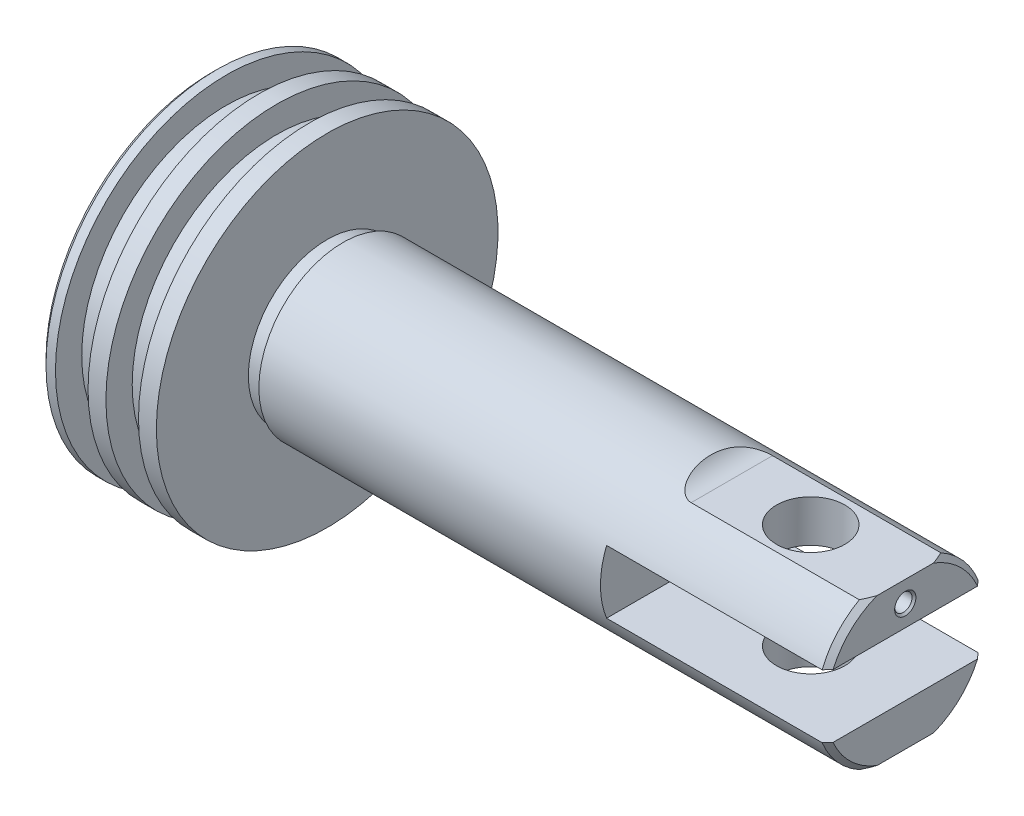
SolidWorks part; units mm, degrees
ref_plane "前视基准面" through (0, 0, 0) normal (0, 0, 1) x (1, 0, 0)
ref_plane "上视基准面" through (0, 0, 0) normal (0, 1, 0) x (1, 0, 0)
ref_plane "右视基准面" through (0, 0, 0) normal (1, 0, 0) x (0, 0, -1)
sketch "草图1" plane through (0, 0, 0) normal (0, 0, 1) x (1, 0, 0)
  line L0 (0, 0) -> (159.647, 0) construction
  line L1 (55, 0) -> (-55, 0) construction
  line L2 (0, 0) -> (0, 32.5)
  line L3 (0, 32.5) -> (2.8, 32.5)
  line L4 (2.8, 32.5) -> (2.8, 27.5)
  line L5 (2.8, 27.5) -> (9, 27.5)
  line L6 (9, 27.5) -> (9, 32.5)
  line L7 (9, 32.5) -> (12.4, 32.5)
  line L8 (12.4, 32.5) -> (12.4, 27.5)
  line L9 (12.4, 27.5) -> (18.6, 27.5)
  line L10 (18.6, 27.5) -> (18.6, 32.5)
  line L11 (18.6, 32.5) -> (22, 32.5)
  line L12 (22, 32.5) -> (22, 15)
  line L13 (22, 15) -> (25, 15)
  line L14 (25, 15) -> (25, 16)
  line L15 (25, 16) -> (132, 16)
  line L16 (132, 16) -> (132, 0)
  line L17 (0, 0) -> (132, 0)
  dimension "D1" = 65
  dimension "D2" = 55
  dimension "D3" = 32
  dimension "D4" = 3
  dimension "D5" = 1
  dimension "D6" = 6.2
  dimension "D7" = 6.2
  dimension "D8" = 3.4
  dimension "D9" = 3.4
  dimension "D10" = 22
  dimension "D11" = 132
revolve "旋转1" add sketch "草图1" angle 360 about L0
chamfer "倒角2" distance 1 angle 45 1 edges at (132, 0, 16)
chamfer "倒角1" distance 1 angle 45 1 edges at (0, 0, 32.5)
sketch "草图2" plane through (0, 0, 0) normal (0, 0, 1) x (1, 0, 0)
  line L0 (135.5427, 0) -> (90, 0)
  line L1 (35.75, 0) -> (-35.75, 0) construction
  line L2 (132, -16) -> (132, 16) construction
  dimension "D1" = 42
extrude "切除-拉伸-薄壁1" cut sketch "草图2" against normal through all and the other way through all thin thin type mid plane wall 12
sketch "草图3" plane through (132, 0, 0) normal (1, 0, 0) x (0, 0, -1)
  line L1 (-35.392, -14) -> (35.392, -14)
  line L2 (-35.392, -14) -> (-35.392, 14)
  line L3 (-35.392, 14) -> (35.392, 14)
  line L4 (35.392, -14) -> (35.392, 14)
  line L5 (-35.392, -14) -> (35.392, 14) construction
  line L6 (-35.392, 14) -> (35.392, -14) construction
  point P0 (0, 0)
  dimension "D1" = 28
extrude "切除-拉伸1" cut sketch "草图3" against normal blind 38 flip side to cut
fillet "圆角1" radius 5 2 edges at (94, -14, 0) (94, 14, 0)
sketch "草图4" plane through (0, 14, 0) normal (0, 1, 0) x (1, 0, 0)
  line L0 (-35.75, 0) -> (35.75, 0) construction
  line L1 (0, -35.75) -> (0, 35.75) construction
  circle A0 centre (114, 0) radius 6.5
  dimension "D1" = 13
  dimension "D2" = 114
extrude "切除-拉伸2" cut sketch "草图4" against normal blind 38
hole_wizard "M4 螺纹孔1" positions "草图5" profile "草图6" tap size "M4" standard "GB" end condition up to next
sketch "草图5" plane through (132, 0, 0) normal (1, 0, 0) x (0, 0, -1)
  line L0 (0, 35.75) -> (0, -35.75) construction
  line L1 (-13.7477, 6) -> (13.7477, 6) construction
  point P0 (0, 10)
  dimension "D1" = 4
sketch "草图6" plane through (132, 10, 0) normal (0, 1, 0) x (0, 0, -1)
  line L0 (0, 0) -> (0, 11.5)
  line L1 (0, 11.5) -> (1.65, 11.5)
  line L2 (1.65, 11.5) -> (1.65, 0.375)
  line L3 (1.65, 0.375) -> (2.025, 0)
  line L5 (2.025, 0) -> (0, 0)
  line L6 (-1.65, 0.375) -> (-2.025, 0) construction
  line L11 (0, -6.35) -> (0, 107.95) construction
  dimension "通孔螺纹孔钻头直径" = 3.3
  dimension "通孔螺纹孔钻头深度" = 11.5
  dimension "近端锥形沉头孔直径" = 4.05
  dimension "近端锥形沉头孔角度" = 90
cosmetic thread "孔螺纹线1" parameters "D2"=4
